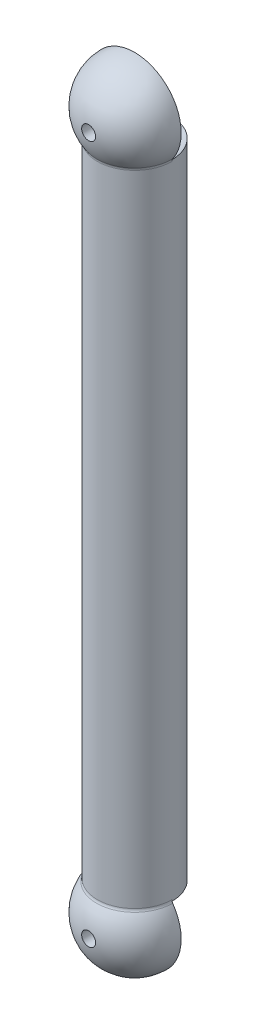
SolidWorks part; units mm, degrees
ref_plane "Front Plane" through (0, 0, 0) normal (0, 0, 1) x (1, 0, 0)
ref_plane "Top Plane" through (0, 0, 0) normal (0, 1, 0) x (1, 0, 0)
ref_plane "Right Plane" through (0, 0, 0) normal (1, 0, 0) x (0, 0, -1)
sketch "Sketch1" plane through (0, 0, 0) normal (0, 0, 1) x (1, 0, 0)
  line L0 (0, 0) -> (0, 150) construction
  line L1 (-8, 6) -> (-8, 144)
  line L2 (0, 160) -> (0, -10)
  arc A0 (-8, 6) -> (0, -10) centre (0, 0) ccw
  arc A1 (0, 160) -> (-8, 144) centre (0, 150) ccw
  dimension "D1" = 20
  dimension "D2" = 150
  dimension "D3" = 8
revolve "Revolve1" add sketch "Sketch1" angle 180 about L0
sketch "Sketch2" plane through (0, 0, 0) normal (0, 0, -1) x (-1, 0, 0)
  circle A0 centre (0, 0) radius 1.5
  circle A2 centre (0, 150) radius 1.5
  point P2 (0, 0)
  point P6 (26.2759, 82.0136)
  point P7 (0, 150)
  dimension "D1" = 3
  dimension "D2" = 3
extrude "Cut-Extrude1" cut sketch "Sketch2" against normal through all
sketch "Sketch3" plane through (0, 0, 0) normal (0, 0, -1) x (-1, 0, 0)
  line L0 (0, 150) -> (0, 0) construction
  line L1 (0, 140) -> (0, 10)
  line L4 (8, 144) -> (8, 6)
  arc A4 (0, 10) -> (8, 6) centre (0, 0) cw
  arc A5 (8, 144) -> (0, 140) centre (0, 150) cw
  arc A6 (8, 144) -> (-8, 144) centre (0, 150) ccw construction
  arc A7 (-8, 6) -> (8, 6) centre (0, 0) ccw construction
  dimension "D1" = 8
revolve "Revolve2" add sketch "Sketch3" angle 180 about L0
fillet "Fillet1" radius 1 2 edges at (0, 6, 8) (0, 144, 8)
